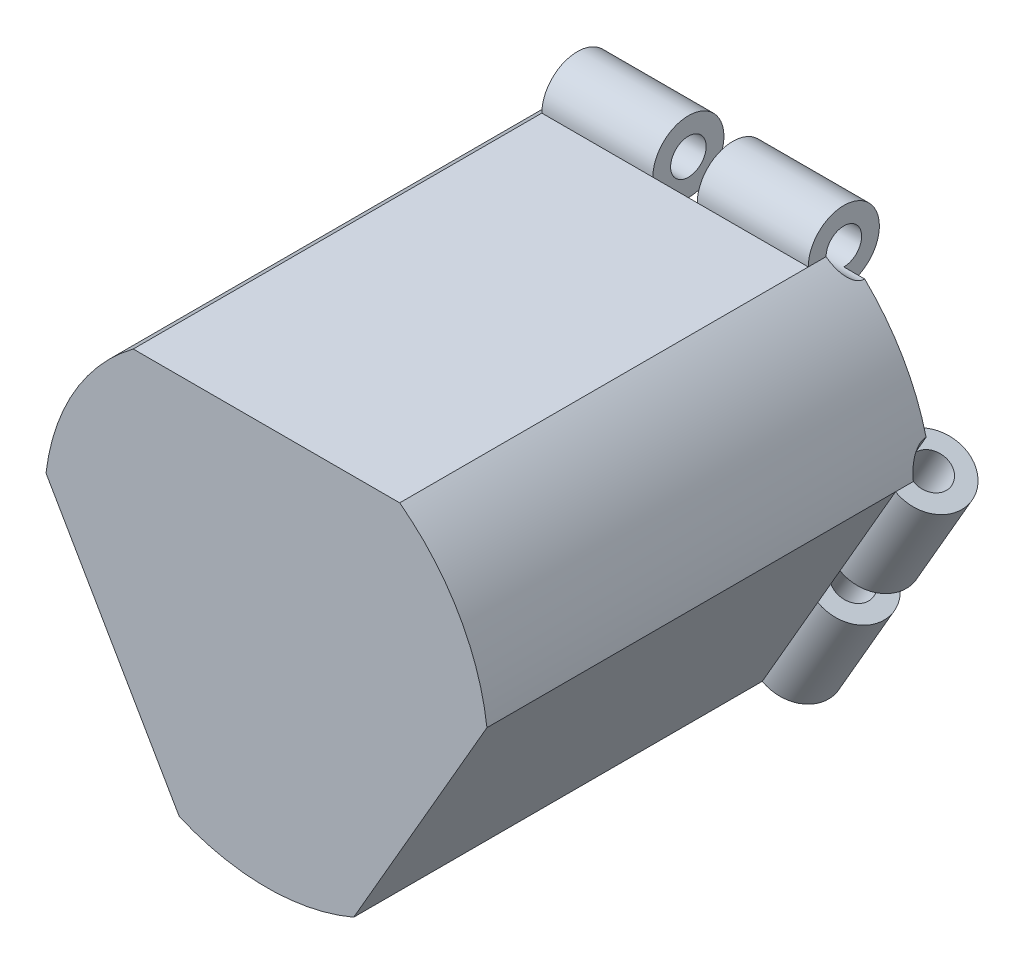
SolidWorks part; units mm, degrees
ref_plane "Alzado" through (0, 0, 0) normal (0, 0, 1) x (1, 0, 0)
ref_plane "Planta" through (0, 0, 0) normal (0, 1, 0) x (1, 0, 0)
ref_plane "Vista lateral" through (0, 0, 0) normal (1, 0, 0) x (0, 0, -1)
sketch "Croquis1" plane through (0, 0, 0) normal (0, 0, 1) x (1, 0, 0)
  circle A0 centre (0, 0) radius 25
  dimension "D1" = 50
extrude "Saliente-Extruir1" add sketch "Croquis1" along normal blind 50
sketch "Croquis2" plane through (0, 0, 0) normal (0, 0, -1) x (-1, 0, 0)
  line L3 (-15, 20) -> (15, 20)
  arc A0 (15, 20) -> (-15, 20) centre (0, 0) ccw
  point P0 (0, 0)
extrude "Cortar-Extruir1" cut sketch "Croquis2" against normal blind 50
pattern_circular "MatrizC2" count 3 every 120 about axis through (0, 0, 50) along (0, 0, -1) of "Cortar-Extruir1"
sketch "Croquis3" plane through (0, 0, 0) normal (0, 0, -1) x (-1, 0, 0)
  line L0 (-15, 20) -> (15, 20) construction
  line L1 (15, 20) -> (15, 24.317) construction
  line L2 (15, 24.317) -> (-15, 24.317) construction
  line L3 (-15, 24.317) -> (-15, 20) construction
sketch "Croquis4" plane through (0, 0, 0) normal (1, 0, 0) x (0, 0, -1)
  circle A0 centre (0, 20) radius 4
  circle A1 centre (0, 20) radius 2
extrude "Saliente-Extruir2" add sketch "Croquis4" along normal up to vertex (15 mm away) and the other way up to vertex (15 mm away) up to point (15, 24.317, 0) other way up to point (-15, 24.317, 0)
extrude "Cortar-Extruir3" cut sketch "Croquis4<2>" along normal blind 20 and the other way blind 20 contours A1
sketch "Croquis4<2>" plane through (0, 0, 0) normal (1, 0, 0) x (0, 0, -1) same geometry as "Croquis4"
pattern_circular "MatrizC3" count 3 over 360 about axis through (0, 0, 50) along (0, 0, -1) of "Saliente-Extruir2"
pattern_circular "MatrizC4" count 3 over 360 about axis through (0, 0, 50) along (0, 0, -1) of "Cortar-Extruir3"
extrude "Cortar-Extruir4" cut sketch "Croquis4<3>" against normal blind 2.5 and the other way blind 2.5
sketch "Croquis4<3>" plane through (0, 0, 0) normal (1, 0, 0) x (0, 0, -1) same geometry as "Croquis4"
pattern_circular "MatrizC5" count 3 over 360 about axis through (0, 0, 50) along (0, 0, -1) of "Cortar-Extruir4"
